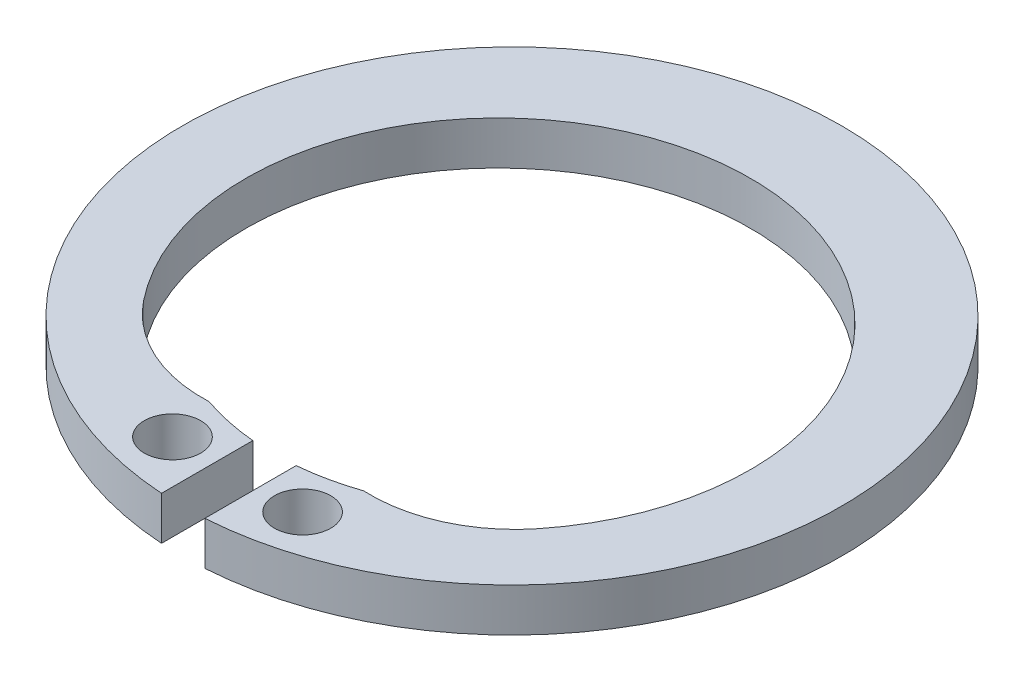
SolidWorks part; units mm, degrees
ref_plane "Front Plane" through (0, 0, 0) normal (0, 0, 1) x (1, 0, 0)
ref_plane "Top Plane" through (0, 0, 0) normal (0, 1, 0) x (1, 0, 0)
ref_plane "Right Plane" through (0, 0, 0) normal (1, 0, 0) x (0, 0, -1)
ref_axis "Axis1" through (0, 0, 0) along (0, 1, 0)
sketch "Sketch1" plane through (0, 0, 0) normal (0, 1, 0) x (1, 0, 0)
  line L0 (0, -0.6956) -> (0, -15043.9996) construction
  line L1 (-0.5, -7.5835) -> (-0.5, -5.4772)
  line L2 (0.5, -7.5835) -> (0.5, -5.4772)
  arc A0 (-0.5, -7.5835) -> (0.5, -7.5835) centre (0, 0) cw
  arc A1 (-0.5, -5.4772) -> (-1.7806, -5.2038) centre (0, 0) cw
  arc A3 (-4.5534, -3.9428) -> (-1.7806, -5.2038) centre (-1.9313, -1.8562) ccw
  arc A4 (4.5534, -3.9428) -> (1.7806, -5.2038) centre (1.9313, -1.8562) cw
  arc A5 (0.5, -5.4772) -> (1.7806, -5.2038) centre (0, 0) ccw
  circle A6 centre (-1.5, -6.3296) radius 0.65
  circle A7 centre (1.5, -6.3296) radius 0.65
  arc A8 (-4.5534, -3.9428) -> (4.5534, -3.9428) centre (0, -0.3192) cw
  point P18 (0, 7.6)
  point P20 (0, 5.5)
  point P21 (2.9986, -6.1496)
  point P22 (0.4741, -7.7713)
  point P23 (6.2921, -1.8028)
  point P24 (2.9986, -4.6579)
  point P25 (4.5534, -3.9428)
  point P26 (1.5775, -6.3001)
  point P27 (-0.5, -6.5304)
  point P28 (1.5, -6.3296)
  dimension "D1" = 1.3
  dimension "D2" = 2.1
  dimension "D3" = 5.5
  dimension "D4" = 5.5
  dimension "D5" = 1
  dimension "D6" = 3
extrude "Boss-Extrude1" add sketch "Sketch1" along normal blind 1
